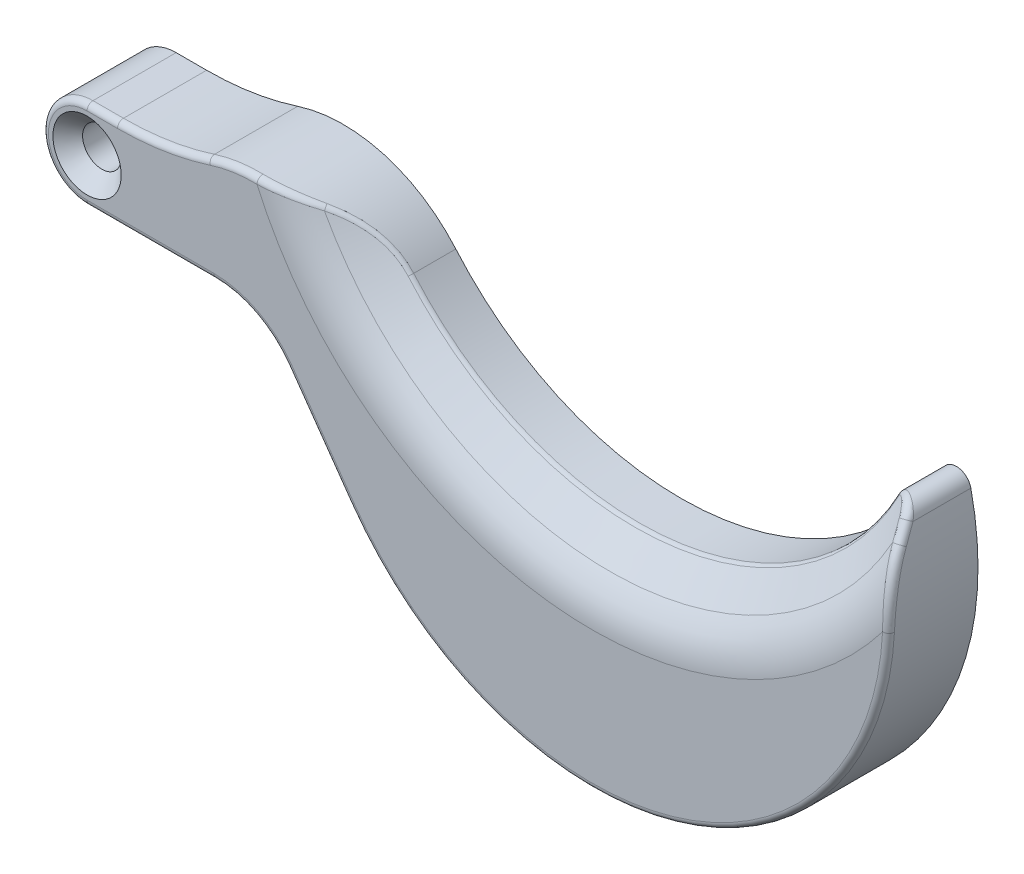
SolidWorks part; units mm, degrees
material "PLA"
ref_plane "前视基准面" through (0, 0, 0) normal (0, 0, 1) x (1, 0, 0)
ref_plane "上视基准面" through (0, 0, 0) normal (0, 1, 0) x (1, 0, 0)
ref_plane "右视基准面" through (0, 0, 0) normal (1, 0, 0) x (0, 0, -1)
sketch "草图1" plane through (0, 0, 0) normal (0, 0, 1) x (1, 0, 0)
  line L0 (-17, -1.5) -> (-11.1753, -1.5)
  line L1 (-25.3128, 0) -> (11.8501, 0) construction
  line L2 (-11.1753, -1.5) -> (-8.1753, -5.7588)
  line L3 (-17, 1.5) -> (-11.1753, 1.5)
  line L4 (-11.1753, 1.5) -> (-8.1753, 5.7588)
  circle A0 centre (-17, 0) radius 0.65
  arc A1 (-8.1753, -5.7588) -> (-8.1753, 5.7588) centre (0, 0) ccw
  arc A2 (-17, 1.5) -> (-17, -1.5) centre (-17, 0) ccw
  dimension "D1" = 20
  dimension "D2" = 1.3
  dimension "D4" = 3
  dimension "D3" = 17
  dimension "D5" = 3
extrude "凸台-拉伸1" add sketch "草图1" along normal blind 3
sketch "草图4" plane through (0, 0, 3) normal (0, 0, 1) x (1, 0, 0)
  line L14 (-8.1753, 5.7588) -> (-11.1753, 1.5) construction
  line L15 (-8.1753, 5.7588) -> (-9.5002, 3.878)
  arc A1 (-9.5002, 3.878) -> (9.3675, 3.5) centre (0, 7) ccw
  arc A8 (-8.1753, -5.7588) -> (-8.1753, 5.7588) centre (0, 0) ccw construction
  arc A9 (9.3675, 3.5) -> (-8.1753, 5.7588) centre (0, 0) ccw
  dimension "D1" = 20
  dimension "D2" = 7
extrude "切除-拉伸2" cut sketch "草图4" against normal blind 3
fillet "圆角4" radius 10 1 edges at (-11.1753, 1.5, 1.5)
fillet "圆角5" radius 5 1 edges at (-9.5002, 3.878, 1.5)
fillet "圆角6" radius 3 1 edges at (-11.1753, -1.5, 1.5)
fillet "圆角7" radius 0.5 1 edges at (9.3675, 3.5, 1.5)
sketch "草图5" plane through (0, 0, 3) normal (0, 0, 1) x (1, 0, 0)
  circle A0 centre (0, 7) radius 11.5
  dimension "D2" = 23
  dimension "D1" = 7
extrude "切除-拉伸3" cut sketch "草图5" against normal blind 3 draft 45
fillet "圆角10" radius 2 1 edges at (-0.527, -4.4879, 3)
fillet "圆角11" radius 0.2 14 edges at (-9.2272, -4.2656, 3) (-11.3502, -1.837, 3) (-14.8658, -1.5, 3) (-18.5, 0, 3) (-16.4868, 1.5, 3) (-14.422, 1.6211, 3) (-12.146, 2.1625, 3) (-10.5509, 2.1538, 2.8667) (-8.3004, 1.165, 1.6461) (1.1049, -2.9388, 1.5) (9.2953, 2.5709, 1.7966) (9.9256, 1.2172, 2.8145) (2.9185, -9.5646, 3)
chamfer "倒角1" distance 0.3 angle 45 1 edges at (-16.35, 0, 0)
chamfer "倒角2" distance 0.5 angle 45 1 edges at (-16.35, 0, 3)
